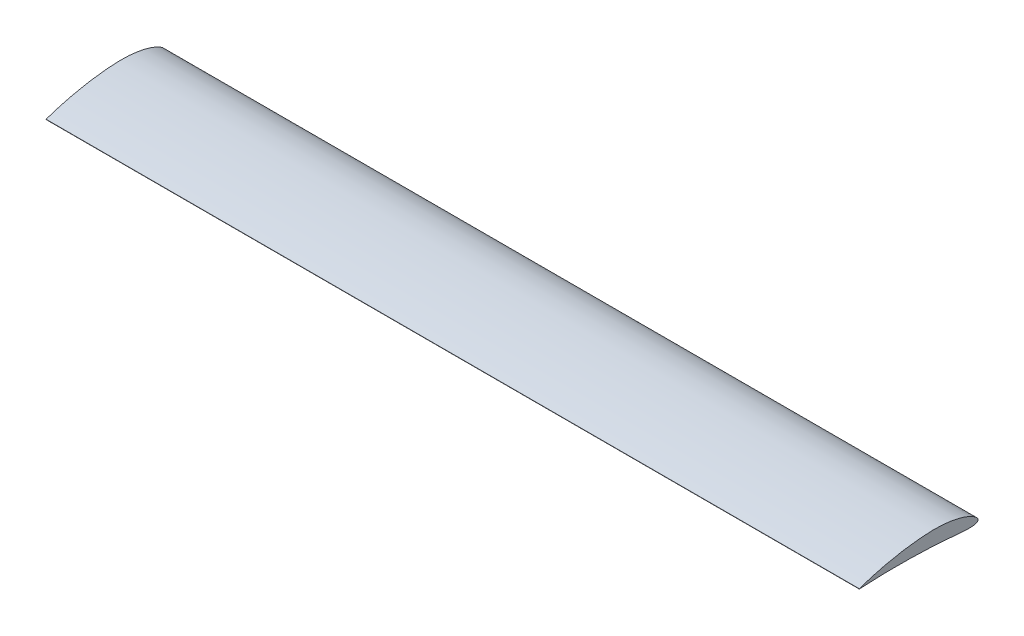
SolidWorks part; units mm, degrees
ref_plane "Front Plane" through (0, 0, 0) normal (0, 0, 1) x (1, 0, 0)
ref_plane "Top Plane" through (0, 0, 0) normal (0, 1, 0) x (1, 0, 0)
ref_plane "Right Plane" through (0, 0, 0) normal (1, 0, 0) x (0, 0, -1)
sketch3d "3DSketch3" plane through (0, 0, 0) normal (0, 0, 1) x (1, 0, 0)
  dimension "D1" = 2438.4
curve "Curve3"
  spline degree 3 poles (0, 0, 0) (0, -0.0634, 0.0198) (0, -0.1901, 0.0592) (0, -0.3772, 0.1273) (0, -0.5618, 0.2018) (0, -0.7437, 0.2832) (0, -0.923, 0.3715) (0, -1.0997, 0.4667) (0, -1.2737, 0.5687) (0, -1.4452, 0.6775) (0, -1.614, 0.7932) (0, -1.7802, 0.9157) (0, -1.9437, 1.045) (0, -2.1047, 1.181) (0, -2.2631, 1.3238) (0, -2.4188, 1.4735) (0, -2.5721, 1.6298) (0, -2.7222, 1.7933) (0, -2.8706, 1.9627) (0, -3.0158, 2.1392) (0, -3.1586, 2.3224) (0, -3.2988, 2.5123) (0, -3.4364, 2.7088) (0, -3.5714, 2.912) (0, -3.7039, 3.1219) (0, -3.8339, 3.3384) (0, -3.9613, 3.5614) (0, -4.0861, 3.7911) (0, -4.2084, 4.0274) (0, -4.3282, 4.2702) (0, -4.4454, 4.5196) (0, -4.5602, 4.7755) (0, -4.6724, 5.0379) (0, -4.7821, 5.3068) (0, -4.8894, 5.5822) (0, -4.9941, 5.8641) (0, -5.0964, 6.1524) (0, -5.1962, 6.4471) (0, -5.2935, 6.7483) (0, -5.3884, 7.0559) (0, -5.4809, 7.3698) (0, -5.5709, 7.6901) (0, -5.6585, 8.0167) (0, -5.7437, 8.3497) (0, -5.8264, 8.6889) (0, -5.9068, 9.0345) (0, -5.9848, 9.3863) (0, -6.0604, 9.7443) (0, -6.1337, 10.1086) (0, -6.2046, 10.4791) (0, -6.2732, 10.8558) (0, -6.3394, 11.2386) (0, -6.4033, 11.6276) (0, -6.4649, 12.0227) (0, -6.5242, 12.4239) (0, -6.5813, 12.8312) (0, -6.636, 13.2445) (0, -6.6885, 13.6639) (0, -6.7388, 14.0893) (0, -6.7868, 14.5207) (0, -6.8326, 14.958) (0, -6.8762, 15.4013) (0, -6.9176, 15.8506) (0, -6.9569, 16.3057) (0, -6.9939, 16.7667) (0, -7.0288, 17.2336) (0, -7.0616, 17.7063) (0, -7.0922, 18.1848) (0, -7.1208, 18.6691) (0, -7.1472, 19.1592) (0, -7.1716, 19.655) (0, -7.1939, 20.1565) (0, -7.2141, 20.6637) (0, -7.2323, 21.1766) (0, -7.2486, 21.6952) (0, -7.2628, 22.2193) (0, -7.275, 22.749) (0, -7.2852, 23.2844) (0, -7.2935, 23.8252) (0, -7.2999, 24.3716) (0, -7.3043, 24.9235) (0, -7.3069, 25.4808) (0, -7.3075, 26.0436) (0, -7.3063, 26.6118) (0, -7.3033, 27.1854) (0, -7.2984, 27.7644) (0, -7.2917, 28.3487) (0, -7.2832, 28.9383) (0, -7.273, 29.5332) (0, -7.2609, 30.1334) (0, -7.2472, 30.7389) (0, -7.2317, 31.3495) (0, -7.2145, 31.9653) (0, -7.1956, 32.5863) (0, -7.1751, 33.2124) (0, -7.1529, 33.8436) (0, -7.1291, 34.4799) (0, -7.1038, 35.1213) (0, -7.0768, 35.7677) (0, -7.0482, 36.4191) (0, -7.0182, 37.0755) (0, -6.9866, 37.7368) (0, -6.9534, 38.403) (0, -6.9189, 39.0741) (0, -6.8828, 39.7501) (0, -6.8453, 40.431) (0, -6.8064, 41.1166) (0, -6.7662, 41.807) (0, -6.7245, 42.5022) (0, -6.6815, 43.2022) (0, -6.6371, 43.9068) (0, -6.5915, 44.6161) (0, -6.5445, 45.3301) (0, -6.4963, 46.0486) (0, -6.4469, 46.7718) (0, -6.3962, 47.4996) (0, -6.3444, 48.2318) (0, -6.2914, 48.9686) (0, -6.2372, 49.7099) (0, -6.1819, 50.4557) (0, -6.1255, 51.2059) (0, -6.068, 51.9604) (0, -6.0095, 52.7194) (0, -5.9499, 53.4827) (0, -5.8894, 54.2503) (0, -5.8278, 55.0222) (0, -5.7653, 55.7984) (0, -5.7018, 56.5788) (0, -5.6375, 57.3635) (0, -5.5722, 58.1523) (0, -5.5061, 58.9453) (0, -5.4392, 59.7424) (0, -5.3714, 60.5436) (0, -5.3029, 61.3488) (0, -5.2336, 62.1581) (0, -5.1635, 62.9715) (0, -5.0927, 63.7888) (0, -5.0213, 64.6101) (0, -4.9492, 65.4353) (0, -4.8764, 66.2644) (0, -4.8031, 67.0974) (0, -4.7291, 67.9343) (0, -4.6546, 68.7749) (0, -4.5796, 69.6194) (0, -4.504, 70.4677) (0, -4.428, 71.3196) (0, -4.3515, 72.1753) (0, -4.2746, 73.0347) (0, -4.1972, 73.8977) (0, -4.1195, 74.7644) (0, -4.0414, 75.6346) (0, -3.9631, 76.5085) (0, -3.8844, 77.3858) (0, -3.8054, 78.2667) (0, -3.7262, 79.1511) (0, -3.6467, 80.0389) (0, -3.5671, 80.9302) (0, -3.4873, 81.8249) (0, -3.4073, 82.7229) (0, -3.3272, 83.6243) (0, -3.247, 84.529) (0, -3.1668, 85.437) (0, -3.0865, 86.3483) (0, -3.0062, 87.2628) (0, -2.926, 88.1805) (0, -2.8457, 89.1014) (0, -2.7656, 90.0255) (0, -2.6855, 90.9526) (0, -2.6055, 91.8829) (0, -2.5257, 92.8162) (0, -2.4461, 93.7526) (0, -2.3666, 94.692) (0, -2.2874, 95.6343) (0, -2.2084, 96.5796) (0, -2.1297, 97.5279) (0, -2.0514, 98.479) (0, -1.9733, 99.433) (0, -1.8956, 100.3898) (0, -1.8182, 101.3494) (0, -1.7413, 102.3118) (0, -1.6648, 103.277) (0, -1.5888, 104.2449) (0, -1.5132, 105.2155) (0, -1.4382, 106.1887) (0, -1.3636, 107.1646) (0, -1.2897, 108.1431) (0, -1.2163, 109.1241) (0, -1.1435, 110.1077) (0, -1.0714, 111.0938) (0, -0.9999, 112.0824) (0, -0.9291, 113.0735) (0, -0.8591, 114.067) (0, -0.7897, 115.0629) (0, -0.7211, 116.0611) (0, -0.6533, 117.0617) (0, -0.5863, 118.0646) (0, -0.5201, 119.0698) (0, -0.4548, 120.0772) (0, -0.3904, 121.0869) (0, -0.3268, 122.0987) (0, -0.2642, 123.1127) (0, -0.2025, 124.1288) (0, -0.1418, 125.147) (0, -0.0821, 126.1672) (0, -0.0234, 127.1895) (0, 0.0343, 128.2138) (0, 0.0908, 129.2401) (0, 0.1464, 130.2683) (0, 0.2008, 131.2984) (0, 0.2541, 132.3304) (0, 0.3062, 133.3643) (0, 0.3572, 134.3999) (0, 0.4069, 135.4374) (0, 0.4555, 136.4765) (0, 0.5028, 137.5174) (0, 0.5489, 138.56) (0, 0.5937, 139.6043) (0, 0.6372, 140.6501) (0, 0.6797, 141.7018) (0, 0.7205, 142.7639) (0, 0.7611, 143.8363) (0, 0.8019, 144.9147) (0, 0.8426, 145.9944) (0, 0.8833, 147.0755) (0, 0.9239, 148.1578) (0, 0.9644, 149.2414) (0, 1.0047, 150.3263) (0, 1.045, 151.4122) (0, 1.0852, 152.4994) (0, 1.1252, 153.5876) (0, 1.165, 154.6768) (0, 1.2047, 155.7671) (0, 1.2442, 156.8584) (0, 1.2835, 157.9505) (0, 1.3226, 159.0436) (0, 1.3615, 160.1375) (0, 1.4001, 161.2323) (0, 1.4385, 162.3278) (0, 1.4767, 163.424) (0, 1.5146, 164.5209) (0, 1.5522, 165.6185) (0, 1.5896, 166.7167) (0, 1.6266, 167.8154) (0, 1.6634, 168.9147) (0, 1.6998, 170.0145) (0, 1.7359, 171.1147) (0, 1.7717, 172.2153) (0, 1.8071, 173.3162) (0, 1.8422, 174.4175) (0, 1.8769, 175.5191) (0, 1.9113, 176.6209) (0, 1.9452, 177.7229) (0, 1.9788, 178.825) (0, 2.0119, 179.9273) (0, 2.0447, 181.0297) (0, 2.077, 182.132) (0, 2.1089, 183.2344) (0, 2.1404, 184.3367) (0, 2.1714, 185.4389) (0, 2.202, 186.541) (0, 2.2321, 187.6429) (0, 2.2617, 188.7446) (0, 2.2909, 189.846) (0, 2.3196, 190.9471) (0, 2.3478, 192.0478) (0, 2.3755, 193.1482) (0, 2.4027, 194.2482) (0, 2.4294, 195.3476) (0, 2.4556, 196.4466) (0, 2.4812, 197.545) (0, 2.5064, 198.6428) (0, 2.531, 199.7399) (0, 2.5551, 200.8364) (0, 2.5786, 201.9321) (0, 2.6016, 203.0271) (0, 2.624, 204.1213) (0, 2.6459, 205.2146) (0, 2.6672, 206.307) (0, 2.688, 207.3985) (0, 2.7082, 208.489) (0, 2.7278, 209.5785) (0, 2.7468, 210.6669) (0, 2.7653, 211.7542) (0, 2.7832, 212.8403) (0, 2.8005, 213.9253) (0, 2.8172, 215.009) (0, 2.8333, 216.0915) (0, 2.8488, 217.1726) (0, 2.8638, 218.2524) (0, 2.8781, 219.3307) (0, 2.8918, 220.4076) (0, 2.905, 221.483) (0, 2.9175, 222.5569) (0, 2.9294, 223.6292) (0, 2.9408, 224.6999) (0, 2.9515, 225.769) (0, 2.9616, 226.8363) (0, 2.9711, 227.9019) (0, 2.98, 228.9657) (0, 2.9883, 230.0277) (0, 2.996, 231.0878) (0, 3.0031, 232.146) (0, 3.0096, 233.2022) (0, 3.0155, 234.2564) (0, 3.0208, 235.3086) (0, 3.0255, 236.3587) (0, 3.0295, 237.4067) (0, 3.033, 238.4525) (0, 3.0359, 239.4962) (0, 3.0382, 240.5375) (0, 3.0399, 241.5766) (0, 3.0409, 242.6133) (0, 3.0414, 243.6477) (0, 3.0414, 244.6796) (0, 3.0407, 245.7091) (0, 3.0394, 246.7361) (0, 3.0376, 247.7605) (0, 3.0352, 248.7824) (0, 3.0322, 249.8016) (0, 3.0287, 250.8182) (0, 3.0245, 251.832) (0, 3.0199, 252.8431) (0, 3.0146, 253.8514) (0, 3.0088, 254.8569) (0, 3.0025, 255.8595) (0, 2.9956, 256.8592) (0, 2.9881, 257.856) (0, 2.9802, 258.8497) (0, 2.9716, 259.8404) (0, 2.9626, 260.828) (0, 2.953, 261.8126) (0, 2.943, 262.7939) (0, 2.9324, 263.7721) (0, 2.9213, 264.747) (0, 2.9097, 265.7186) (0, 2.8976, 266.6869) (0, 2.885, 267.6519) (0, 2.8719, 268.6135) (0, 2.8583, 269.5716) (0, 2.8443, 270.5262) (0, 2.8298, 271.4773) (0, 2.8148, 272.4249) (0, 2.7994, 273.3689) (0, 2.7835, 274.3092) (0, 2.7672, 275.2459) (0, 2.7505, 276.1788) (0, 2.7333, 277.108) (0, 2.7157, 278.0334) (0, 2.6977, 278.955) (0, 2.6793, 279.8726) (0, 2.6604, 280.7864) (0, 2.6412, 281.6963) (0, 2.6216, 282.6021) (0, 2.6016, 283.504) (0, 2.5813, 284.4017) (0, 2.5606, 285.2954) (0, 2.5395, 286.1849) (0, 2.518, 287.0703) (0, 2.4963, 287.9514) (0, 2.4742, 288.8283) (0, 2.4517, 289.701) (0, 2.429, 290.5693) (0, 2.4059, 291.4332) (0, 2.3825, 292.2927) (0, 2.3588, 293.1478) (0, 2.3349, 293.9985) (0, 2.3106, 294.8446) (0, 2.2861, 295.6862) (0, 2.2613, 296.5232) (0, 2.2363, 297.3556) (0, 2.211, 298.1834) (0, 2.1855, 299.0064) (0, 2.1597, 299.8248) (0, 2.1337, 300.6384) (0, 2.1075, 301.4472) (0, 2.0811, 302.2512) (0, 2.0545, 303.0503) (0, 2.0277, 303.8445) (0, 2.0008, 304.6338) (0, 1.9736, 305.4182) (0, 1.9463, 306.1975) (0, 1.9188, 306.9718) (0, 1.8912, 307.7411) (0, 1.8634, 308.5052) (0, 1.8355, 309.2643) (0, 1.8074, 310.0181) (0, 1.7793, 310.7668) (0, 1.751, 311.5103) (0, 1.7227, 312.2485) (0, 1.6942, 312.9814) (0, 1.6657, 313.709) (0, 1.6371, 314.4312) (0, 1.6084, 315.148) (0, 1.5796, 315.8594) (0, 1.5508, 316.5654) (0, 1.522, 317.2659) (0, 1.4931, 317.9609) (0, 1.4642, 318.6503) (0, 1.4353, 319.3342) (0, 1.4064, 320.0125) (0, 1.3774, 320.6851) (0, 1.3485, 321.3521) (0, 1.3195, 322.0133) (0, 1.2906, 322.6689) (0, 1.2618, 323.3187) (0, 1.2329, 323.9628) (0, 1.2041, 324.601) (0, 1.1754, 325.2334) (0, 1.1467, 325.86) (0, 1.118, 326.4806) (0, 1.0895, 327.0953) (0, 1.061, 327.7041) (0, 1.0326, 328.3069) (0, 1.0043, 328.9038) (0, 0.9761, 329.4946) (0, 0.9481, 330.0793) (0, 0.9201, 330.658) (0, 0.8923, 331.2305) (0, 0.8646, 331.797) (0, 0.837, 332.3572) (0, 0.8096, 332.9113) (0, 0.7823, 333.4592) (0, 0.7552, 334.0009) (0, 0.7282, 334.5363) (0, 0.7014, 335.0654) (0, 0.6748, 335.5883) (0, 0.6484, 336.1048) (0, 0.6222, 336.6149) (0, 0.5962, 337.1187) (0, 0.5704, 337.6161) (0, 0.5448, 338.1071) (0, 0.5194, 338.5916) (0, 0.4942, 339.0697) (0, 0.4693, 339.5413) (0, 0.4445, 340.0064) (0, 0.4201, 340.465) (0, 0.3959, 340.917) (0, 0.3719, 341.3625) (0, 0.3482, 341.8013) (0, 0.3247, 342.2336) (0, 0.3016, 342.6593) (0, 0.2787, 343.0782) (0, 0.2561, 343.4906) (0, 0.2337, 343.8962) (0, 0.2117, 344.2952) (0, 0.1899, 344.6874) (0, 0.1685, 345.0729) (0, 0.1473, 345.4516) (0, 0.1265, 345.8236) (0, 0.106, 346.1887) (0, 0.0858, 346.5471) (0, 0.0659, 346.8986) (0, 0.0464, 347.2433) (0, 0.027, 347.5812) (0, 0.0083, 347.9122) (0, -0.0102, 348.2362) (0, -0.0286, 348.5534) (0, -0.0462, 348.8637) (0, -0.0638, 349.167) (0, -0.0809, 349.4634) (0, -0.0977, 349.7529) (0, -0.1141, 350.0353) (0, -0.1301, 350.3108) (0, -0.1458, 350.5793) (0, -0.161, 350.8408) (0, -0.1759, 351.0952) (0, -0.1905, 351.3427) (0, -0.2046, 351.583) (0, -0.2183, 351.8164) (0, -0.2317, 352.0426) (0, -0.2447, 352.2618) (0, -0.2572, 352.4739) (0, -0.2694, 352.6789) (0, -0.2811, 352.8768) (0, -0.2925, 353.0675) (0, -0.3034, 353.2512) (0, -0.314, 353.4277) (0, -0.3241, 353.5971) (0, -0.3338, 353.7593) (0, -0.3431, 353.9144) (0, -0.352, 354.0623) (0, -0.3604, 354.203) (0, -0.3684, 354.3365) (0, -0.3761, 354.4629) (0, -0.3832, 354.5821) (0, -0.39, 354.6941) (0, -0.3963, 354.7989) (0, -0.4022, 354.8964) (0, -0.4077, 354.9868) (0, -0.4127, 355.07) (0, -0.4173, 355.1459) (0, -0.4214, 355.2146) (0, -0.4252, 355.2761) (0, -0.4285, 355.3304) (0, -0.4313, 355.3774) (0, -0.4337, 355.4172) (0, -0.4357, 355.4498) (0, -0.4372, 355.4751) (0, -0.4383, 355.4932) (0, -0.439, 355.5041) (0, -0.4393, 355.5089) (0, -0.4394, 355.5101) knots 0 0 0 0 0.000556 0.001111 0.001666 0.002222 0.00278 0.00334 0.003902 0.004469 0.00504 0.005616 0.006197 0.006785 0.00738 0.007983 0.008593 0.009214 0.009841 0.010479 0.011127 0.011786 0.012455 0.013136 0.013829 0.014533 0.01525 0.01598 0.016722 0.017478 0.018247 0.019029 0.019826 0.020637 0.021461 0.022301 0.023154 0.024023 0.024906 0.025805 0.026718 0.027647 0.028591 0.02955 0.030525 0.031515 0.032521 0.033542 0.034579 0.035632 0.036701 0.037785 0.038885 0.040001 0.041133 0.042281 0.043445 0.044625 0.04582 0.047032 0.048259 0.049503 0.050762 0.052037 0.053328 0.054635 0.055957 0.057296 0.05865 0.06002 0.061406 0.062807 0.064224 0.065656 0.067104 0.068568 0.070047 0.071541 0.073051 0.074576 0.076117 0.077673 0.079244 0.08083 0.082431 0.084047 0.085678 0.087324 0.088985 0.09066 0.092351 0.094056 0.095775 0.097509 0.099258 0.101021 0.102798 0.10459 0.106396 0.108216 0.11005 0.111898 0.11376 0.115636 0.117525 0.119428 0.121345 0.123276 0.12522 0.127177 0.129148 0.131132 0.133129 0.135139 0.137163 0.139199 0.141248 0.14331 0.145385 0.147472 0.149572 0.151684 0.153809 0.155946 0.158095 0.160257 0.16243 0.164616 0.166813 0.169023 0.171244 0.173476 0.175721 0.177977 0.180244 0.182523 0.184813 0.187114 0.189426 0.191749 0.194083 0.196428 0.198784 0.20115 0.203527 0.205915 0.208313 0.210721 0.21314 0.215569 0.218008 0.220456 0.222915 0.225384 0.227862 0.23035 0.232848 0.235355 0.237872 0.240398 0.242933 0.245478 0.248031 0.250593 0.253165 0.255745 0.258334 0.260932 0.263538 0.266153 0.268776 0.271407 0.274047 0.276695 0.27935 0.282014 0.284686 0.287366 0.290053 0.292748 0.29545 0.29816 0.300878 0.303602 0.306334 0.309073 0.311819 0.314572 0.317332 0.320099 0.322872 0.325652 0.328439 0.331232 0.334031 0.336836 0.339648 0.342466 0.34529 0.34812 0.350956 0.353797 0.356644 0.359497 0.362355 0.365219 0.368088 0.370962 0.373841 0.376726 0.379615 0.382509 0.385408 0.388312 0.391221 0.394134 0.397051 0.399973 0.402899 0.405865 0.408873 0.411885 0.414901 0.417921 0.420944 0.423971 0.427001 0.430035 0.433071 0.436111 0.439153 0.442199 0.445246 0.448297 0.45135 0.454405 0.457463 0.460523 0.463585 0.466648 0.469714 0.472781 0.475849 0.47892 0.481991 0.485064 0.488137 0.491212 0.494288 0.497364 0.500441 0.503518 0.506596 0.509674 0.512753 0.515831 0.518909 0.521987 0.525065 0.528142 0.531219 0.534296 0.537371 0.540445 0.543519 0.546591 0.549663 0.552733 0.555801 0.558868 0.561933 0.564996 0.568057 0.571117 0.574174 0.577228 0.580281 0.583331 0.586378 0.589422 0.592464 0.595502 0.598538 0.60157 0.604599 0.607624 0.610646 0.613664 0.616678 0.619688 0.622694 0.625696 0.628694 0.631687 0.634676 0.63766 0.64064 0.643614 0.646584 0.649548 0.652507 0.655461 0.658409 0.661352 0.664289 0.66722 0.670145 0.673065 0.675978 0.678884 0.681785 0.684679 0.687566 0.690446 0.69332 0.696186 0.699046 0.701898 0.704743 0.707581 0.710411 0.713233 0.716048 0.718854 0.721653 0.724443 0.727226 0.729999 0.732765 0.735522 0.73827 0.741009 0.74374 0.746461 0.749174 0.751877 0.75457 0.757255 0.759929 0.762594 0.765249 0.767895 0.77053 0.773155 0.77577 0.778374 0.780968 0.783552 0.786125 0.788687 0.791238 0.793778 0.796307 0.798825 0.801332 0.803827 0.806311 0.808783 0.811243 0.813691 0.816128 0.818552 0.820965 0.823365 0.825753 0.828128 0.830491 0.832841 0.835178 0.837503 0.839814 0.842113 0.844398 0.84667 0.848929 0.851174 0.853406 0.855624 0.857829 0.86002 0.862196 0.864359 0.866508 0.868642 0.870762 0.872868 0.874959 0.877036 0.879098 0.881145 0.883178 0.885195 0.887198 0.889185 0.891157 0.893114 0.895056 0.896982 0.898892 0.900787 0.902667 0.90453 0.906378 0.908209 0.910025 0.911824 0.913608 0.915375 0.917125 0.91886 0.920577 0.922279 0.923963 0.925631 0.927282 0.928916 0.930533 0.932133 0.933716 0.935282 0.93683 0.938362 0.939875 0.941372 0.942851 0.944312 0.945756 0.947181 0.94859 0.94998 0.951352 0.952707 0.954043 0.955361 0.956661 0.957943 0.959206 0.960452 0.961678 0.962887 0.964077 0.965248 0.966401 0.967535 0.96865 0.969746 0.970824 0.971883 0.972923 0.973944 0.974945 0.975928 0.976892 0.977837 0.978762 0.979668 0.980555 0.981422 0.98227 0.983099 0.983908 0.984698 0.985468 0.986219 0.98695 0.987662 0.988353 0.989026 0.989678 0.990311 0.990923 0.991517 0.99209 0.992643 0.993177 0.99369 0.994184 0.994657 0.995111 0.995544 0.995958 0.996352 0.996725 0.997078 0.997412 0.997725 0.998018 0.998291 0.998543 0.998776 0.998988 0.99918 0.999352 0.999504 0.999636 0.999747 0.999838 0.999909 0.99996 0.99999 1 1 1 1
curve "Curve4"
  spline degree 3 poles (0, 0, 0) (0, 0.0638, -0.0184) (0, 0.1913, -0.0552) (0, 0.385, -0.1013) (0, 0.5801, -0.1407) (0, 0.7768, -0.1727) (0, 0.9752, -0.1976) (0, 1.1751, -0.2151) (0, 1.3767, -0.2255) (0, 1.5798, -0.2285) (0, 1.7845, -0.2243) (0, 1.9908, -0.2128) (0, 2.1987, -0.1941) (0, 2.4081, -0.168) (0, 2.6191, -0.1347) (0, 2.8317, -0.0941) (0, 3.0458, -0.0461) (0, 3.2614, 0.0091) (0, 3.4786, 0.0716) (0, 3.6973, 0.1414) (0, 3.9175, 0.2185) (0, 4.1392, 0.303) (0, 4.3625, 0.3947) (0, 4.5872, 0.4938) (0, 4.8133, 0.6002) (0, 5.041, 0.7139) (0, 5.2701, 0.8349) (0, 5.5006, 0.9632) (0, 5.7325, 1.0989) (0, 5.9659, 1.2419) (0, 6.2006, 1.3922) (0, 6.4368, 1.5498) (0, 6.6743, 1.7147) (0, 6.9131, 1.887) (0, 7.1533, 2.0666) (0, 7.3948, 2.2535) (0, 7.6375, 2.4477) (0, 7.8816, 2.6493) (0, 8.1269, 2.8582) (0, 8.3735, 3.0743) (0, 8.6213, 3.2978) (0, 8.8703, 3.5286) (0, 9.1204, 3.7667) (0, 9.3718, 4.0122) (0, 9.6242, 4.2649) (0, 9.8778, 4.5249) (0, 10.1325, 4.7921) (0, 10.3882, 5.0667) (0, 10.645, 5.3486) (0, 10.9028, 5.6377) (0, 11.1616, 5.9341) (0, 11.4214, 6.2378) (0, 11.6822, 6.5487) (0, 11.9438, 6.8668) (0, 12.2064, 7.1922) (0, 12.4698, 7.5249) (0, 12.734, 7.8648) (0, 12.9991, 8.2118) (0, 13.265, 8.5661) (0, 13.5316, 8.9276) (0, 13.7989, 9.2963) (0, 14.067, 9.6722) (0, 14.3357, 10.0553) (0, 14.6051, 10.4455) (0, 14.875, 10.8428) (0, 15.1456, 11.2473) (0, 15.4167, 11.659) (0, 15.6883, 12.0777) (0, 15.9604, 12.5036) (0, 16.233, 12.9366) (0, 16.5059, 13.3766) (0, 16.7793, 13.8237) (0, 17.0531, 14.2779) (0, 17.3271, 14.7391) (0, 17.6015, 15.2073) (0, 17.8761, 15.6825) (0, 18.1509, 16.1648) (0, 18.4259, 16.654) (0, 18.7011, 17.1502) (0, 18.9764, 17.6533) (0, 19.2518, 18.1634) (0, 19.5272, 18.6804) (0, 19.8026, 19.2042) (0, 20.078, 19.735) (0, 20.3534, 20.2726) (0, 20.6287, 20.8171) (0, 20.9038, 21.3684) (0, 21.1787, 21.9265) (0, 21.4535, 22.4914) (0, 21.728, 23.0631) (0, 22.0023, 23.6415) (0, 22.2762, 24.2266) (0, 22.5498, 24.8185) (0, 22.8229, 25.417) (0, 23.0957, 26.0222) (0, 23.368, 26.634) (0, 23.6398, 27.2524) (0, 23.911, 27.8775) (0, 24.1817, 28.5091) (0, 24.4517, 29.1472) (0, 24.7211, 29.7919) (0, 24.9898, 30.443) (0, 25.2577, 31.1007) (0, 25.5249, 31.7648) (0, 25.7913, 32.4353) (0, 26.0568, 33.1122) (0, 26.3214, 33.7954) (0, 26.5851, 34.485) (0, 26.8478, 35.1809) (0, 27.1096, 35.8831) (0, 27.3702, 36.5916) (0, 27.6298, 37.3062) (0, 27.8883, 38.0271) (0, 28.1456, 38.7542) (0, 28.4017, 39.4873) (0, 28.6566, 40.2266) (0, 28.9102, 40.972) (0, 29.1625, 41.7234) (0, 29.4134, 42.4808) (0, 29.6629, 43.2442) (0, 29.911, 44.0136) (0, 30.1577, 44.7888) (0, 30.4028, 45.57) (0, 30.6464, 46.357) (0, 30.8884, 47.1498) (0, 31.1287, 47.9484) (0, 31.3674, 48.7528) (0, 31.6044, 49.5628) (0, 31.8397, 50.3786) (0, 32.0732, 51.2) (0, 32.3049, 52.0269) (0, 32.5347, 52.8595) (0, 32.7627, 53.6976) (0, 32.9887, 54.5412) (0, 33.2128, 55.3902) (0, 33.4349, 56.2446) (0, 33.6549, 57.1045) (0, 33.8729, 57.9697) (0, 34.0888, 58.8401) (0, 34.3026, 59.7159) (0, 34.5141, 60.5968) (0, 34.7235, 61.483) (0, 34.9306, 62.3743) (0, 35.1355, 63.2707) (0, 35.338, 64.1721) (0, 35.5382, 65.0786) (0, 35.736, 65.99) (0, 35.9314, 66.9064) (0, 36.1244, 67.8277) (0, 36.3149, 68.7538) (0, 36.5029, 69.6847) (0, 36.6883, 70.6204) (0, 36.8712, 71.5608) (0, 37.0514, 72.5059) (0, 37.229, 73.4556) (0, 37.404, 74.4099) (0, 37.5762, 75.3688) (0, 37.7458, 76.3321) (0, 37.9125, 77.2999) (0, 38.0765, 78.2721) (0, 38.2377, 79.2486) (0, 38.396, 80.2295) (0, 38.5514, 81.2146) (0, 38.704, 82.204) (0, 38.8536, 83.1975) (0, 39.0002, 84.1951) (0, 39.1439, 85.1968) (0, 39.2846, 86.2026) (0, 39.4222, 87.2123) (0, 39.5567, 88.2259) (0, 39.6882, 89.2434) (0, 39.8166, 90.2648) (0, 39.9418, 91.2899) (0, 40.0639, 92.3188) (0, 40.1828, 93.3514) (0, 40.2985, 94.3876) (0, 40.4109, 95.4274) (0, 40.5202, 96.4707) (0, 40.6261, 97.5175) (0, 40.7287, 98.5677) (0, 40.8281, 99.6213) (0, 40.9241, 100.6783) (0, 41.0167, 101.7385) (0, 41.106, 102.8019) (0, 41.1919, 103.8686) (0, 41.2744, 104.9383) (0, 41.3534, 106.0112) (0, 41.429, 107.087) (0, 41.5011, 108.1658) (0, 41.5698, 109.2476) (0, 41.635, 110.3322) (0, 41.6966, 111.4196) (0, 41.7548, 112.5098) (0, 41.8094, 113.6026) (0, 41.8604, 114.6982) (0, 41.9079, 115.7963) (0, 41.9518, 116.897) (0, 41.9921, 118.0002) (0, 42.0288, 119.1058) (0, 42.0619, 120.2138) (0, 42.0913, 121.3241) (0, 42.1173, 122.4368) (0, 42.139, 123.5516) (0, 42.1592, 124.6686) (0, 42.1676, 125.7878) (0, 42.1543, 126.9092) (0, 42.1994, 128.032) (0, 42.1931, 129.1574) (0, 42.196, 130.2845) (0, 42.1917, 131.4134) (0, 42.1846, 132.5441) (0, 42.1736, 133.6766) (0, 42.1589, 134.8108) (0, 42.1405, 135.9466) (0, 42.1183, 137.0839) (0, 42.0925, 138.2228) (0, 42.0629, 139.3632) (0, 42.0295, 140.505) (0, 41.9927, 141.6439) (0, 41.9519, 142.7753) (0, 41.9085, 143.8991) (0, 41.8633, 145.0197) (0, 41.8158, 146.1414) (0, 41.7661, 147.2644) (0, 41.7142, 148.3885) (0, 41.66, 149.5137) (0, 41.6037, 150.64) (0, 41.5452, 151.7672) (0, 41.4845, 152.8954) (0, 41.4216, 154.0245) (0, 41.3565, 155.1544) (0, 41.2893, 156.2851) (0, 41.2199, 157.4166) (0, 41.1484, 158.5488) (0, 41.0747, 159.6817) (0, 40.9989, 160.8151) (0, 40.921, 161.9492) (0, 40.841, 163.0837) (0, 40.7588, 164.2187) (0, 40.6746, 165.3541) (0, 40.5883, 166.4899) (0, 40.4999, 167.626) (0, 40.4094, 168.7624) (0, 40.3169, 169.8991) (0, 40.2223, 171.0359) (0, 40.1257, 172.1728) (0, 40.0271, 173.3098) (0, 39.9265, 174.4469) (0, 39.8238, 175.5839) (0, 39.7192, 176.7209) (0, 39.6126, 177.8578) (0, 39.504, 178.9945) (0, 39.3935, 180.1311) (0, 39.281, 181.2674) (0, 39.1666, 182.4033) (0, 39.0503, 183.539) (0, 38.9321, 184.6743) (0, 38.8119, 185.8091) (0, 38.6899, 186.9434) (0, 38.5661, 188.0773) (0, 38.4404, 189.2105) (0, 38.3128, 190.3431) (0, 38.1834, 191.4751) (0, 38.0523, 192.6063) (0, 37.9193, 193.7368) (0, 37.7845, 194.8665) (0, 37.648, 195.9953) (0, 37.5097, 197.1232) (0, 37.3697, 198.2502) (0, 37.228, 199.3761) (0, 37.0845, 200.5011) (0, 36.9394, 201.6249) (0, 36.7926, 202.7477) (0, 36.6441, 203.8692) (0, 36.494, 204.9895) (0, 36.3423, 206.1086) (0, 36.1889, 207.2263) (0, 36.034, 208.3427) (0, 35.8775, 209.4577) (0, 35.7194, 210.5712) (0, 35.5598, 211.6833) (0, 35.3986, 212.7938) (0, 35.236, 213.9027) (0, 35.0718, 215.01) (0, 34.9062, 216.1157) (0, 34.7391, 217.2196) (0, 34.5706, 218.3217) (0, 34.4007, 219.4221) (0, 34.2293, 220.5206) (0, 34.0566, 221.6172) (0, 33.8825, 222.7119) (0, 33.707, 223.8046) (0, 33.5303, 224.8953) (0, 33.3522, 225.9839) (0, 33.1728, 227.0704) (0, 32.9921, 228.1547) (0, 32.8102, 229.2369) (0, 32.6271, 230.3168) (0, 32.4427, 231.3944) (0, 32.2571, 232.4697) (0, 32.0704, 233.5427) (0, 31.8825, 234.6132) (0, 31.6935, 235.6813) (0, 31.5033, 236.7469) (0, 31.3121, 237.81) (0, 31.1197, 238.8704) (0, 30.9263, 239.9283) (0, 30.7319, 240.9835) (0, 30.5365, 242.036) (0, 30.34, 243.0858) (0, 30.1426, 244.1328) (0, 29.9443, 245.1769) (0, 29.7449, 246.2182) (0, 29.5447, 247.2566) (0, 29.3436, 248.2921) (0, 29.1416, 249.3245) (0, 28.9388, 250.354) (0, 28.7351, 251.3804) (0, 28.5307, 252.4036) (0, 28.3254, 253.4238) (0, 28.1194, 254.4407) (0, 27.9126, 255.4544) (0, 27.7051, 256.4649) (0, 27.4969, 257.472) (0, 27.2881, 258.4759) (0, 27.0785, 259.4763) (0, 26.8684, 260.4733) (0, 26.6576, 261.4669) (0, 26.4463, 262.457) (0, 26.2343, 263.4435) (0, 26.0219, 264.4265) (0, 25.8089, 265.4059) (0, 25.5954, 266.3816) (0, 25.3814, 267.3537) (0, 25.167, 268.322) (0, 24.9521, 269.2866) (0, 24.7368, 270.2474) (0, 24.5212, 271.2043) (0, 24.3051, 272.1574) (0, 24.0888, 273.1066) (0, 23.8721, 274.0519) (0, 23.6551, 274.9932) (0, 23.4378, 275.9305) (0, 23.2203, 276.8637) (0, 23.0026, 277.7929) (0, 22.7847, 278.718) (0, 22.5665, 279.6389) (0, 22.3483, 280.5556) (0, 22.1299, 281.4682) (0, 21.9113, 282.3764) (0, 21.6927, 283.2804) (0, 21.4741, 284.1801) (0, 21.2553, 285.0754) (0, 21.0366, 285.9664) (0, 20.8179, 286.8529) (0, 20.5992, 287.735) (0, 20.3805, 288.6126) (0, 20.162, 289.4856) (0, 19.9435, 290.3542) (0, 19.7252, 291.2181) (0, 19.507, 292.0775) (0, 19.2889, 292.9322) (0, 19.0711, 293.7822) (0, 18.8535, 294.6275) (0, 18.6361, 295.4681) (0, 18.419, 296.3039) (0, 18.2022, 297.1349) (0, 17.9857, 297.9611) (0, 17.7695, 298.7825) (0, 17.5537, 299.5989) (0, 17.3383, 300.4104) (0, 17.1233, 301.217) (0, 16.9087, 302.0186) (0, 16.6945, 302.8152) (0, 16.4809, 303.6068) (0, 16.2677, 304.3933) (0, 16.0551, 305.1747) (0, 15.843, 305.951) (0, 15.6315, 306.7221) (0, 15.4205, 307.4881) (0, 15.2102, 308.2488) (0, 15.0006, 309.0043) (0, 14.7916, 309.7546) (0, 14.5833, 310.4996) (0, 14.3757, 311.2392) (0, 14.1688, 311.9736) (0, 13.9627, 312.7025) (0, 13.7573, 313.4261) (0, 13.5528, 314.1443) (0, 13.3491, 314.857) (0, 13.1463, 315.5642) (0, 12.9443, 316.266) (0, 12.7432, 316.9622) (0, 12.543, 317.6529) (0, 12.3438, 318.338) (0, 12.1455, 319.0176) (0, 11.9482, 319.6915) (0, 11.752, 320.3598) (0, 11.5567, 321.0224) (0, 11.3625, 321.6793) (0, 11.1694, 322.3306) (0, 10.9774, 322.9761) (0, 10.7865, 323.6158) (0, 10.5967, 324.2498) (0, 10.4081, 324.8779) (0, 10.2207, 325.5003) (0, 10.0345, 326.1168) (0, 9.8495, 326.7274) (0, 9.6658, 327.3322) (0, 9.4833, 327.931) (0, 9.3021, 328.5239) (0, 9.1223, 329.1109) (0, 8.9437, 329.6919) (0, 8.7665, 330.2669) (0, 8.5907, 330.8359) (0, 8.4163, 331.3989) (0, 8.2433, 331.9558) (0, 8.0718, 332.5067) (0, 7.9016, 333.0515) (0, 7.733, 333.5902) (0, 7.5659, 334.1227) (0, 7.4002, 334.6492) (0, 7.2362, 335.1694) (0, 7.0736, 335.6835) (0, 6.9126, 336.1914) (0, 6.7533, 336.6931) (0, 6.5955, 337.1885) (0, 6.4394, 337.6777) (0, 6.2849, 338.1607) (0, 6.1321, 338.6374) (0, 5.9809, 339.1078) (0, 5.8315, 339.5718) (0, 5.6838, 340.0296) (0, 5.5378, 340.481) (0, 5.3936, 340.926) (0, 5.2511, 341.3647) (0, 5.1105, 341.797) (0, 4.9716, 342.2229) (0, 4.8346, 342.6424) (0, 4.6994, 343.0554) (0, 4.5661, 343.462) (0, 4.4346, 343.8622) (0, 4.305, 344.2559) (0, 4.1774, 344.6431) (0, 4.0516, 345.0238) (0, 3.9278, 345.398) (0, 3.8059, 345.7657) (0, 3.686, 346.1268) (0, 3.5681, 346.4814) (0, 3.4521, 346.8294) (0, 3.3385, 347.171) (0, 3.2253, 347.5055) (0, 3.12, 347.8366) (0, 2.9939, 348.1528) (0, 2.8977, 348.4717) (0, 2.7952, 348.7798) (0, 2.6918, 349.0804) (0, 2.5994, 349.3774) (0, 2.5004, 349.6649) (0, 2.4056, 349.947) (0, 2.3123, 350.2222) (0, 2.2214, 350.4907) (0, 2.1326, 350.7526) (0, 2.0459, 351.0078) (0, 1.9614, 351.2562) (0, 1.8792, 351.498) (0, 1.7991, 351.733) (0, 1.7212, 351.9613) (0, 1.6456, 352.1828) (0, 1.5722, 352.3977) (0, 1.501, 352.6057) (0, 1.432, 352.807) (0, 1.3654, 353.0016) (0, 1.3009, 353.1894) (0, 1.2388, 353.3704) (0, 1.1789, 353.5446) (0, 1.1214, 353.712) (0, 1.0661, 353.8727) (0, 1.0131, 354.0265) (0, 0.9624, 354.1736) (0, 0.9141, 354.3138) (0, 0.8681, 354.4472) (0, 0.8243, 354.5738) (0, 0.783, 354.6936) (0, 0.7439, 354.8066) (0, 0.7072, 354.9127) (0, 0.6729, 355.012) (0, 0.6409, 355.1045) (0, 0.6112, 355.1901) (0, 0.5839, 355.2689) (0, 0.559, 355.3408) (0, 0.5364, 355.4059) (0, 0.5162, 355.4642) (0, 0.4984, 355.5156) (0, 0.483, 355.5602) (0, 0.4699, 355.5979) (0, 0.4592, 355.6287) (0, 0.4509, 355.6527) (0, 0.4449, 355.6698) (0, 0.4413, 355.6801) (0, 0.4397, 355.6847) (0, 0.4394, 355.6858) knots 0 0 0 0 0.000533 0.001065 0.001598 0.002131 0.002665 0.003202 0.003742 0.004285 0.004833 0.005386 0.005944 0.006508 0.00708 0.007659 0.008245 0.008841 0.009445 0.01006 0.010684 0.011319 0.011964 0.012621 0.01329 0.013971 0.014664 0.01537 0.016089 0.016821 0.017567 0.018327 0.0191 0.019888 0.020691 0.021508 0.02234 0.023187 0.024049 0.024927 0.02582 0.026728 0.027653 0.028593 0.029548 0.03052 0.031508 0.032513 0.033533 0.03457 0.035623 0.036692 0.037778 0.03888 0.039999 0.041135 0.042287 0.043456 0.044641 0.045843 0.047062 0.048297 0.04955 0.050819 0.052104 0.053407 0.054726 0.056061 0.057414 0.058783 0.060169 0.061571 0.062991 0.064426 0.065879 0.067348 0.068833 0.070335 0.071853 0.073388 0.07494 0.076507 0.078091 0.079692 0.081308 0.082941 0.08459 0.086255 0.087936 0.089633 0.091346 0.093075 0.09482 0.096581 0.098358 0.10015 0.101958 0.103781 0.10562 0.107475 0.109344 0.11123 0.11313 0.115046 0.116977 0.118923 0.120884 0.122859 0.12485 0.126856 0.128876 0.130911 0.13296 0.135024 0.137103 0.139196 0.141303 0.143424 0.145559 0.147709 0.149872 0.152049 0.15424 0.156445 0.158664 0.160896 0.163141 0.1654 0.167672 0.169957 0.172256 0.174567 0.176892 0.179229 0.181579 0.183942 0.186317 0.188705 0.191105 0.193517 0.195942 0.198379 0.200828 0.203289 0.205761 0.208246 0.210742 0.213249 0.215768 0.218299 0.220841 0.223393 0.225957 0.228532 0.231118 0.233714 0.236322 0.238939 0.241568 0.244206 0.246855 0.249514 0.252183 0.254862 0.257551 0.26025 0.262958 0.265676 0.268403 0.271139 0.273885 0.27664 0.279404 0.282177 0.284959 0.287749 0.290548 0.293355 0.296171 0.298995 0.301827 0.304668 0.307516 0.310372 0.313236 0.316107 0.318986 0.321873 0.324766 0.327667 0.330575 0.33349 0.336412 0.33934 0.342275 0.345217 0.348165 0.351119 0.35408 0.357046 0.360019 0.362997 0.365982 0.368971 0.371967 0.374967 0.377974 0.380985 0.384002 0.387023 0.390049 0.39308 0.396116 0.399156 0.4022 0.405249 0.408302 0.411359 0.41442 0.417451 0.420448 0.42345 0.426455 0.429463 0.432474 0.435489 0.438507 0.441528 0.444552 0.447578 0.450607 0.453639 0.456672 0.459708 0.462747 0.465787 0.468829 0.471873 0.474918 0.477965 0.481014 0.484064 0.487114 0.490166 0.493219 0.496273 0.499327 0.502382 0.505438 0.508493 0.511549 0.514605 0.517661 0.520717 0.523773 0.526828 0.529883 0.532937 0.53599 0.539043 0.542094 0.545144 0.548194 0.551241 0.554288 0.557332 0.560375 0.563417 0.566456 0.569493 0.572528 0.575561 0.578591 0.581619 0.584644 0.587666 0.590685 0.593702 0.596715 0.599725 0.602732 0.605735 0.608734 0.61173 0.614722 0.61771 0.620694 0.623674 0.626649 0.62962 0.632587 0.635548 0.638506 0.641458 0.644405 0.647347 0.650284 0.653215 0.656141 0.659061 0.661976 0.664885 0.667788 0.670684 0.673575 0.67646 0.679338 0.682209 0.685074 0.687932 0.690784 0.693628 0.696465 0.699296 0.702119 0.704934 0.707742 0.710543 0.713335 0.71612 0.718897 0.721666 0.724426 0.727179 0.729923 0.732658 0.735385 0.738104 0.740813 0.743513 0.746205 0.748887 0.75156 0.754224 0.756878 0.759523 0.762158 0.764783 0.767399 0.770004 0.7726 0.775185 0.77776 0.780324 0.782879 0.785422 0.787955 0.790477 0.792988 0.795488 0.797977 0.800455 0.802922 0.805377 0.807821 0.810253 0.812673 0.815082 0.817479 0.819863 0.822236 0.824597 0.826945 0.829281 0.831605 0.833916 0.836215 0.8385 0.840773 0.843033 0.84528 0.847514 0.849735 0.851943 0.854137 0.856318 0.858485 0.860639 0.862779 0.864905 0.867017 0.869116 0.8712 0.87327 0.875326 0.877368 0.879396 0.881409 0.883407 0.885391 0.88736 0.889314 0.891254 0.893178 0.895088 0.896982 0.898861 0.900725 0.902574 0.904407 0.906225 0.908028 0.909814 0.911585 0.913341 0.91508 0.916804 0.918511 0.920203 0.921878 0.923537 0.92518 0.926807 0.928417 0.930011 0.931588 0.933149 0.934693 0.936221 0.937731 0.939225 0.940702 0.942162 0.943605 0.945031 0.94644 0.947831 0.949206 0.950563 0.951902 0.953225 0.954529 0.955817 0.957086 0.958338 0.959573 0.960789 0.961988 0.963169 0.964332 0.965477 0.966605 0.967714 0.968805 0.969878 0.970933 0.97197 0.972988 0.973988 0.97497 0.975933 0.976878 0.977805 0.978722 0.979608 0.980478 0.98133 0.98216 0.982975 0.983771 0.984549 0.985308 0.986048 0.986769 0.987471 0.988155 0.988819 0.989465 0.990091 0.990699 0.991287 0.991857 0.992407 0.992939 0.993451 0.993944 0.994418 0.994872 0.995308 0.995724 0.996121 0.996499 0.996857 0.997196 0.997516 0.997817 0.998098 0.99836 0.998602 0.998825 0.999029 0.999214 0.999379 0.999524 0.99965 0.999757 0.999845 0.999913 0.999961 0.99999 1 1 1 1
sketch "Sketch1" plane through (0, 0, 0) normal (1, 0, 0) x (0, 0, -1)
  arc A0 (-355.6858, 0.4394) -> (-355.5101, -0.4394) centre (-355.598, 0) ccw
  spline S0 degree 3 poles (4752.6647, -1547.1568) (-26.3578, 29.3158) (3.2903, 9.0146) (-0.1273, -0.3772) (-0.2018, -0.5618) (-0.2832, -0.7437) (-0.4012, -0.9833) (-0.5329, -1.2173) (-0.6775, -1.4452) (-0.8325, -1.6713) (-1.0005, -1.8912) (-1.181, -2.1047) (-1.3238, -2.2631) (-1.4735, -2.4188) (-1.6298, -2.5721) (-1.7933, -2.7222) (-1.9627, -2.8706) (-2.1392, -3.0158) (-2.3224, -3.1586) (-2.5777, -3.3471) (-2.8444, -3.5288) (-3.1943, -3.7496) (-3.4875, -3.9211) (-3.8704, -4.1292) (-4.2734, -4.3326) (-4.779, -4.5644) (-5.3107, -4.7862) (-5.8682, -4.998) (-6.4515, -5.1999) (-7.0604, -5.392) (-7.6948, -5.5743) (-8.3546, -5.7469) (-9.0395, -5.9099) (-9.7495, -6.0633) (-10.4843, -6.2073) (-11.2439, -6.342) (-12.0281, -6.4674) (-12.8366, -6.5836) (-13.6694, -6.6907) (-14.5262, -6.7889) (-15.4069, -6.8781) (-16.3112, -6.9586) (-17.2391, -7.0305) (-18.1904, -7.0938) (-19.1647, -7.1487) (-20.1621, -7.1953) (-21.3587, -7.2403) (-22.7637, -7.2781) (-24.3862, -7.3027) (-26.0581, -7.31) (-27.7787, -7.3006) (-29.5474, -7.2749) (-31.3635, -7.2334) (-33.2262, -7.1766) (-35.1349, -7.105) (-37.0889, -7.0192) (-39.0874, -6.9198) (-41.1296, -6.8072) (-43.215, -6.6821) (-45.5868, -6.5292) (-48.2549, -6.3449) (-51.2283, -6.1257) (-54.2722, -5.8892) (-57.3847, -5.6371) (-60.5642, -5.3708) (-63.8088, -5.0919) (-67.1168, -4.802) (-70.4864, -4.5027) (-74.2095, -4.1695) (-78.2945, -3.8026) (-82.7495, -3.4042) (-87.2882, -3.0028) (-91.907, -2.6018) (-96.6025, -2.2045) (-101.3711, -1.814) (-106.2091, -1.4337) (-111.4464, -1.0417) (-117.426, -0.6222) (-122.1112, -0.3228) (-125.147, -0.1418) (-126.1672, -0.0821) (-127.1895, -0.0234) (-128.2138, 0.0343) (-129.2401, 0.0908) (-130.9568, 0.1835) (-133.7157, 0.326) (-136.4798, 0.457) (-138.56, 0.5489) (-139.6043, 0.5937) (-140.6501, 0.6372) (-141.7018, 0.6797) (-142.7639, 0.7205) (-143.8363, 0.7611) (-144.9147, 0.8019) (-146.7164, 0.8698) (-151.0617, 1.0328) (-157.2371, 1.2597) (-164.8952, 1.5295) (-172.2208, 1.7748) (-179.9282, 2.0153) (-187.639, 2.2357) (-195.3391, 2.4332) (-203.0139, 2.6056) (-210.6489, 2.751) (-218.5854, 2.8736) (-226.7995, 2.9675) (-235.2648, 3.0268) (-243.5969, 3.0476) (-252.1036, 3.0301) (-260.7451, 2.9708) (-269.4791, 2.8666) (-278.2268, 2.7192) (-287.211, 2.5227) (-296.5993, 2.2676) (-305.9588, 1.9627) (-315.3182, 1.6092) (-324.5863, 1.2126) (-333.7568, 0.7743) (-340.5803, 0.4167) (-344.5208, 0.1994) (-345.6973, 0.1336) (-346.1887, 0.106) (-346.5471, 0.0858) (-346.8986, 0.0659) (-347.2433, 0.0464) (-347.5812, 0.027) (-347.9122, 0.0083) (-348.2362, -0.0102) (-348.5534, -0.0286) (-348.8637, -0.0462) (-349.167, -0.0638) (-349.5576, -0.0863) (-350.3629, -0.1331) (-351.9429, -0.2255) (-353.6898, -0.3294) (-354.9871, -0.4076) (-355.4172, -0.4337) (-355.4932, -0.4383) (-374.664, -1.6018) (-393.8478, -2.4506) (-110.1537, -4993.2029) knots -0.081994 -0.081994 -0.081994 -0.081994 0.000556 0.001111 0.001666 0.002222 0.00278 0.003902 0.004469 0.00504 0.006197 0.006785 0.00738 0.007983 0.008593 0.009214 0.009841 0.010479 0.011127 0.011786 0.013136 0.013829 0.01525 0.01598 0.017478 0.019029 0.020637 0.022301 0.024023 0.025805 0.027647 0.02955 0.031515 0.033542 0.035632 0.037785 0.040001 0.042281 0.044625 0.047032 0.049503 0.052037 0.054635 0.057296 0.06002 0.062807 0.065656 0.070047 0.074576 0.079244 0.084047 0.088985 0.094056 0.099258 0.10459 0.11005 0.115636 0.121345 0.127177 0.133129 0.141248 0.149572 0.158095 0.166813 0.175721 0.184813 0.194083 0.203527 0.21314 0.225384 0.237872 0.250593 0.263538 0.276695 0.290053 0.303602 0.317332 0.334031 0.353797 0.356644 0.359497 0.362355 0.365219 0.368088 0.370962 0.379615 0.391221 0.394134 0.397051 0.399973 0.402899 0.405865 0.408873 0.411885 0.414901 0.423971 0.448297 0.466648 0.488137 0.509674 0.531219 0.552733 0.574174 0.595502 0.616678 0.64064 0.664289 0.687566 0.710411 0.735522 0.759929 0.783552 0.808783 0.835178 0.862196 0.887198 0.913608 0.939875 0.964077 0.970824 0.972923 0.973944 0.974945 0.975928 0.976892 0.977837 0.978762 0.979668 0.980555 0.981422 0.98227 0.983099 0.984698 0.989026 0.996352 0.999352 0.999909 0.99996 0.99999 1.160736 1.160736 1.160736 1.160736 only from (0, 0) to (-355.5101, -0.4394) construction
  spline S1 degree 3 poles (4819.2495, -1324.3094) (-38.1571, -9.9504) (-2.2131, -9.3316) (0.1013, 0.385) (0.1407, 0.5801) (0.1727, 0.7768) (0.2059, 1.0419) (0.2245, 1.3098) (0.2285, 1.5798) (0.2243, 1.7845) (0.2089, 2.061) (0.1789, 2.3394) (0.1347, 2.6191) (0.0941, 2.8317) (0.0461, 3.0458) (-0.0091, 3.2614) (-0.0716, 3.4786) (-0.1414, 3.6973) (-0.2451, 3.9934) (-0.3628, 4.2901) (-0.528, 4.6648) (-0.6749, 4.9673) (-0.8767, 5.3492) (-1.0529, 5.6575) (-1.2913, 6.0466) (-1.5506, 6.4426) (-1.8882, 6.919) (-2.255, 7.4006) (-2.6511, 7.8875) (-3.0764, 8.3794) (-3.531, 8.8761) (-4.0148, 9.3775) (-4.5277, 9.8835) (-5.0698, 10.3939) (-5.6409, 10.9084) (-6.2412, 11.4269) (-6.8704, 11.9492) (-7.5286, 12.4751) (-8.2157, 13.0043) (-8.9316, 13.5367) (-9.6763, 14.072) (-10.4496, 14.61) (-11.2516, 15.1505) (-12.0821, 15.6931) (-12.9409, 16.2377) (-13.8281, 16.784) (-14.7436, 17.3317) (-15.6871, 17.8806) (-16.8267, 18.5255) (-18.1757, 19.2633) (-19.7475, 20.0892) (-21.3809, 20.9147) (-23.0756, 21.7387) (-24.831, 22.5602) (-26.6466, 23.3781) (-28.5216, 24.1915) (-30.4555, 24.9994) (-32.4477, 25.8007) (-34.4974, 26.5943) (-36.6038, 27.3792) (-38.7663, 28.1544) (-41.2388, 29.0066) (-44.0358, 29.9266) (-47.1717, 30.9034) (-50.4001, 31.8543) (-53.7186, 32.7769) (-57.1251, 33.6687) (-60.6169, 34.5275) (-64.1917, 35.351) (-67.8467, 36.1371) (-71.8991, 36.9474) (-76.3606, 37.7648) (-81.2419, 38.5699) (-86.2286, 39.3025) (-91.3147, 39.9592) (-96.4941, 40.5371) (-101.7606, 41.0332) (-107.4715, 41.4731) (-112.5261, 41.7678) (-116.1655, 41.925) (-118.0002, 41.9921) (-119.1058, 42.0288) (-120.2138, 42.0619) (-121.3241, 42.0913) (-122.4368, 42.1173) (-123.5516, 42.139) (-124.6686, 42.1592) (-125.7878, 42.1676) (-126.9092, 42.1543) (-128.032, 42.1994) (-129.1574, 42.1931) (-130.2845, 42.196) (-131.4134, 42.1917) (-132.5441, 42.1846) (-133.6766, 42.1736) (-134.8108, 42.1589) (-136.3263, 42.1343) (-137.8438, 42.1023) (-139.3632, 42.0629) (-140.505, 42.0295) (-141.6439, 41.9927) (-142.7753, 41.9519) (-143.8991, 41.9085) (-145.0197, 41.8633) (-147.2669, 41.7681) (-151.0229, 41.591) (-157.05, 41.2551) (-164.229, 40.7746) (-172.1783, 40.1414) (-180.1317, 39.4091) (-188.0731, 38.5818) (-195.9862, 37.664) (-204.2264, 36.6131) (-212.7684, 35.4206) (-221.5847, 34.0793) (-230.631, 32.5925) (-239.8682, 30.9577) (-249.2548, 29.1746) (-258.7207, 27.2571) (-267.9004, 25.2794) (-277.3604, 23.1234) (-286.6899, 20.8796) (-296.3861, 18.4185) (-305.2417, 16.0538) (-313.6987, 13.6943) (-321.6139, 11.3977) (-329.0303, 9.1589) (-336.687, 6.7692) (-341.9168, 5.0788) (-345.2711, 3.9698) (-345.7657, 3.8059) (-346.1268, 3.686) (-346.4814, 3.5681) (-346.8294, 3.4521) (-347.171, 3.3385) (-347.5055, 3.2253) (-347.8366, 3.12) (-348.1528, 2.9939) (-348.4717, 2.8977) (-348.7798, 2.7952) (-349.0804, 2.6918) (-349.3774, 2.5994) (-349.6649, 2.5004) (-349.947, 2.4056) (-350.2222, 2.3123) (-350.4907, 2.2214) (-350.9944, 2.0505) (-351.8316, 1.7658) (-353.0188, 1.3599) (-354.3254, 0.9105) (-355.2145, 0.6029) (-355.6698, 0.4449) (-368.3719, -3.9637) (-381.216, -7.9448) (1245.2072, -4735.1993) knots -0.078568 -0.078568 -0.078568 -0.078568 0.000533 0.001065 0.001598 0.002131 0.002665 0.003742 0.004285 0.004833 0.005386 0.006508 0.00708 0.007659 0.008245 0.008841 0.009445 0.01006 0.010684 0.011964 0.012621 0.013971 0.014664 0.016089 0.016821 0.018327 0.019888 0.021508 0.023187 0.024927 0.026728 0.028593 0.03052 0.032513 0.03457 0.036692 0.03888 0.041135 0.043456 0.045843 0.048297 0.050819 0.053407 0.056061 0.058783 0.061571 0.064426 0.067348 0.070335 0.07494 0.079692 0.08459 0.089633 0.09482 0.10015 0.10562 0.11123 0.116977 0.122859 0.128876 0.135024 0.141303 0.149872 0.158664 0.167672 0.176892 0.186317 0.195942 0.205761 0.215768 0.225957 0.238939 0.252183 0.265676 0.279404 0.293355 0.307516 0.321873 0.33934 0.348165 0.351119 0.35408 0.357046 0.360019 0.362997 0.365982 0.368971 0.371967 0.374967 0.377974 0.380985 0.384002 0.387023 0.390049 0.39308 0.396116 0.399156 0.405249 0.408302 0.411359 0.41442 0.417451 0.420448 0.42345 0.426455 0.438507 0.453639 0.474918 0.496273 0.517661 0.539043 0.560375 0.581619 0.605735 0.62962 0.653215 0.679338 0.704934 0.729923 0.756878 0.780324 0.807821 0.833916 0.860639 0.881409 0.904407 0.926807 0.943605 0.968805 0.970933 0.97197 0.972988 0.973988 0.97497 0.975933 0.976878 0.977805 0.978722 0.979608 0.980478 0.98133 0.98216 0.982975 0.983771 0.984549 0.985308 0.986048 0.988819 0.992407 0.996121 0.999913 0.999961 0.99999 1.107861 1.107861 1.107861 1.107861 only from (0, 0) to (-355.6858, 0.4394) construction
  spline S2 degree 3 poles (0, 0) (-0.0198, -0.0634) (-0.0592, -0.1901) (-0.1273, -0.3772) (-0.2018, -0.5618) (-0.2832, -0.7437) (-0.4012, -0.9833) (-0.5329, -1.2173) (-0.6775, -1.4452) (-0.8325, -1.6713) (-1.0005, -1.8912) (-1.181, -2.1047) (-1.3238, -2.2631) (-1.4735, -2.4188) (-1.6298, -2.5721) (-1.7933, -2.7222) (-1.9627, -2.8706) (-2.1392, -3.0158) (-2.3224, -3.1586) (-2.5777, -3.3471) (-2.8444, -3.5288) (-3.1943, -3.7496) (-3.4875, -3.9211) (-3.8704, -4.1292) (-4.2734, -4.3326) (-4.779, -4.5644) (-5.3107, -4.7862) (-5.8682, -4.998) (-6.4515, -5.1999) (-7.0604, -5.392) (-7.6948, -5.5743) (-8.3546, -5.7469) (-9.0395, -5.9099) (-9.7495, -6.0633) (-10.4843, -6.2073) (-11.2439, -6.342) (-12.0281, -6.4674) (-12.8366, -6.5836) (-13.6694, -6.6907) (-14.5262, -6.7889) (-15.4069, -6.8781) (-16.3112, -6.9586) (-17.2391, -7.0305) (-18.1904, -7.0938) (-19.1647, -7.1487) (-20.1621, -7.1953) (-21.3587, -7.2403) (-22.7637, -7.2781) (-24.3862, -7.3027) (-26.0581, -7.31) (-27.7787, -7.3006) (-29.5474, -7.2749) (-31.3635, -7.2334) (-33.2262, -7.1766) (-35.1349, -7.105) (-37.0889, -7.0192) (-39.0874, -6.9198) (-41.1296, -6.8072) (-43.215, -6.6821) (-45.5868, -6.5292) (-48.2549, -6.3449) (-51.2283, -6.1257) (-54.2722, -5.8892) (-57.3847, -5.6371) (-60.5642, -5.3708) (-63.8088, -5.0919) (-67.1168, -4.802) (-70.4864, -4.5027) (-74.2095, -4.1695) (-78.2945, -3.8026) (-82.7495, -3.4042) (-87.2882, -3.0028) (-91.907, -2.6018) (-96.6025, -2.2045) (-101.3711, -1.814) (-106.2091, -1.4337) (-111.4464, -1.0417) (-117.426, -0.6222) (-122.1112, -0.3228) (-125.147, -0.1418) (-126.1672, -0.0821) (-127.1895, -0.0234) (-128.2138, 0.0343) (-129.2401, 0.0908) (-130.9568, 0.1835) (-133.7157, 0.326) (-136.4798, 0.457) (-138.56, 0.5489) (-139.6043, 0.5937) (-140.6501, 0.6372) (-141.7018, 0.6797) (-142.7639, 0.7205) (-143.8363, 0.7611) (-144.9147, 0.8019) (-146.7164, 0.8698) (-151.0617, 1.0328) (-157.2371, 1.2597) (-164.8952, 1.5295) (-172.2208, 1.7748) (-179.9282, 2.0153) (-187.639, 2.2357) (-195.3391, 2.4332) (-203.0139, 2.6056) (-210.6489, 2.751) (-218.5854, 2.8736) (-226.7995, 2.9675) (-235.2648, 3.0268) (-243.5969, 3.0476) (-252.1036, 3.0301) (-260.7451, 2.9708) (-269.4791, 2.8666) (-278.2268, 2.7192) (-287.211, 2.5227) (-296.5993, 2.2676) (-305.9588, 1.9627) (-315.3182, 1.6092) (-324.5863, 1.2126) (-333.7568, 0.7743) (-340.5803, 0.4167) (-344.5208, 0.1994) (-345.6973, 0.1336) (-346.1887, 0.106) (-346.5471, 0.0858) (-346.8986, 0.0659) (-347.2433, 0.0464) (-347.5812, 0.027) (-347.9122, 0.0083) (-348.2362, -0.0102) (-348.5534, -0.0286) (-348.8637, -0.0462) (-349.167, -0.0638) (-349.5576, -0.0863) (-350.3629, -0.1331) (-351.9429, -0.2255) (-353.7562, -0.3333) (-355.0643, -0.4123) (-355.4992, -0.4387) (-355.5101, -0.4394) knots 0 0 0 0 0.000556 0.001111 0.001666 0.002222 0.00278 0.003902 0.004469 0.00504 0.006197 0.006785 0.00738 0.007983 0.008593 0.009214 0.009841 0.010479 0.011127 0.011786 0.013136 0.013829 0.01525 0.01598 0.017478 0.019029 0.020637 0.022301 0.024023 0.025805 0.027647 0.02955 0.031515 0.033542 0.035632 0.037785 0.040001 0.042281 0.044625 0.047032 0.049503 0.052037 0.054635 0.057296 0.06002 0.062807 0.065656 0.070047 0.074576 0.079244 0.084047 0.088985 0.094056 0.099258 0.10459 0.11005 0.115636 0.121345 0.127177 0.133129 0.141248 0.149572 0.158095 0.166813 0.175721 0.184813 0.194083 0.203527 0.21314 0.225384 0.237872 0.250593 0.263538 0.276695 0.290053 0.303602 0.317332 0.334031 0.353797 0.356644 0.359497 0.362355 0.365219 0.368088 0.370962 0.379615 0.391221 0.394134 0.397051 0.399973 0.402899 0.405865 0.408873 0.411885 0.414901 0.423971 0.448297 0.466648 0.488137 0.509674 0.531219 0.552733 0.574174 0.595502 0.616678 0.64064 0.664289 0.687566 0.710411 0.735522 0.759929 0.783552 0.808783 0.835178 0.862196 0.887198 0.913608 0.939875 0.964077 0.970824 0.972923 0.973944 0.974945 0.975928 0.976892 0.977837 0.978762 0.979668 0.980555 0.981422 0.98227 0.983099 0.984698 0.989026 0.996352 0.999909 1 1 1 1
  spline S3 degree 3 poles (0, 0) (0.0184, 0.0638) (0.0552, 0.1913) (0.1013, 0.385) (0.1407, 0.5801) (0.1727, 0.7768) (0.2059, 1.0419) (0.2245, 1.3098) (0.2285, 1.5798) (0.2243, 1.7845) (0.2089, 2.061) (0.1789, 2.3394) (0.1347, 2.6191) (0.0941, 2.8317) (0.0461, 3.0458) (-0.0091, 3.2614) (-0.0716, 3.4786) (-0.1414, 3.6973) (-0.2451, 3.9934) (-0.3628, 4.2901) (-0.528, 4.6648) (-0.6749, 4.9673) (-0.8767, 5.3492) (-1.0529, 5.6575) (-1.2913, 6.0466) (-1.5506, 6.4426) (-1.8882, 6.919) (-2.255, 7.4006) (-2.6511, 7.8875) (-3.0764, 8.3794) (-3.531, 8.8761) (-4.0148, 9.3775) (-4.5277, 9.8835) (-5.0698, 10.3939) (-5.6409, 10.9084) (-6.2412, 11.4269) (-6.8704, 11.9492) (-7.5286, 12.4751) (-8.2157, 13.0043) (-8.9316, 13.5367) (-9.6763, 14.072) (-10.4496, 14.61) (-11.2516, 15.1505) (-12.0821, 15.6931) (-12.9409, 16.2377) (-13.8281, 16.784) (-14.7436, 17.3317) (-15.6871, 17.8806) (-16.8267, 18.5255) (-18.1757, 19.2633) (-19.7475, 20.0892) (-21.3809, 20.9147) (-23.0756, 21.7387) (-24.831, 22.5602) (-26.6466, 23.3781) (-28.5216, 24.1915) (-30.4555, 24.9994) (-32.4477, 25.8007) (-34.4974, 26.5943) (-36.6038, 27.3792) (-38.7663, 28.1544) (-41.2388, 29.0066) (-44.0358, 29.9266) (-47.1717, 30.9034) (-50.4001, 31.8543) (-53.7186, 32.7769) (-57.1251, 33.6687) (-60.6169, 34.5275) (-64.1917, 35.351) (-67.8467, 36.1371) (-71.8991, 36.9474) (-76.3606, 37.7648) (-81.2419, 38.5699) (-86.2286, 39.3025) (-91.3147, 39.9592) (-96.4941, 40.5371) (-101.7606, 41.0332) (-107.4715, 41.4731) (-112.5261, 41.7678) (-116.1655, 41.925) (-118.0002, 41.9921) (-119.1058, 42.0288) (-120.2138, 42.0619) (-121.3241, 42.0913) (-122.4368, 42.1173) (-123.5516, 42.139) (-124.6686, 42.1592) (-125.7878, 42.1676) (-126.9092, 42.1543) (-128.032, 42.1994) (-129.1574, 42.1931) (-130.2845, 42.196) (-131.4134, 42.1917) (-132.5441, 42.1846) (-133.6766, 42.1736) (-134.8108, 42.1589) (-136.3263, 42.1343) (-137.8438, 42.1023) (-139.3632, 42.0629) (-140.505, 42.0295) (-141.6439, 41.9927) (-142.7753, 41.9519) (-143.8991, 41.9085) (-145.0197, 41.8633) (-147.2669, 41.7681) (-151.0229, 41.591) (-157.05, 41.2551) (-164.229, 40.7746) (-172.1783, 40.1414) (-180.1317, 39.4091) (-188.0731, 38.5818) (-195.9862, 37.664) (-204.2264, 36.6131) (-212.7684, 35.4206) (-221.5847, 34.0793) (-230.631, 32.5925) (-239.8682, 30.9577) (-249.2548, 29.1746) (-258.7207, 27.2571) (-267.9004, 25.2794) (-277.3604, 23.1234) (-286.6899, 20.8796) (-296.3861, 18.4185) (-305.2417, 16.0538) (-313.6987, 13.6943) (-321.6139, 11.3977) (-329.0303, 9.1589) (-336.687, 6.7692) (-341.9168, 5.0788) (-345.2711, 3.9698) (-345.7657, 3.8059) (-346.1268, 3.686) (-346.4814, 3.5681) (-346.8294, 3.4521) (-347.171, 3.3385) (-347.5055, 3.2253) (-347.8366, 3.12) (-348.1528, 2.9939) (-348.4717, 2.8977) (-348.7798, 2.7952) (-349.0804, 2.6918) (-349.3774, 2.5994) (-349.6649, 2.5004) (-349.947, 2.4056) (-350.2222, 2.3123) (-350.4907, 2.2214) (-350.9944, 2.0505) (-351.8316, 1.7658) (-353.0188, 1.3599) (-354.3254, 0.9105) (-355.2191, 0.6013) (-355.6756, 0.4429) (-355.6858, 0.4394) knots 0 0 0 0 0.000533 0.001065 0.001598 0.002131 0.002665 0.003742 0.004285 0.004833 0.005386 0.006508 0.00708 0.007659 0.008245 0.008841 0.009445 0.01006 0.010684 0.011964 0.012621 0.013971 0.014664 0.016089 0.016821 0.018327 0.019888 0.021508 0.023187 0.024927 0.026728 0.028593 0.03052 0.032513 0.03457 0.036692 0.03888 0.041135 0.043456 0.045843 0.048297 0.050819 0.053407 0.056061 0.058783 0.061571 0.064426 0.067348 0.070335 0.07494 0.079692 0.08459 0.089633 0.09482 0.10015 0.10562 0.11123 0.116977 0.122859 0.128876 0.135024 0.141303 0.149872 0.158664 0.167672 0.176892 0.186317 0.195942 0.205761 0.215768 0.225957 0.238939 0.252183 0.265676 0.279404 0.293355 0.307516 0.321873 0.33934 0.348165 0.351119 0.35408 0.357046 0.360019 0.362997 0.365982 0.368971 0.371967 0.374967 0.377974 0.380985 0.384002 0.387023 0.390049 0.39308 0.396116 0.399156 0.405249 0.408302 0.411359 0.41442 0.417451 0.420448 0.42345 0.426455 0.438507 0.453639 0.474918 0.496273 0.517661 0.539043 0.560375 0.581619 0.605735 0.62962 0.653215 0.679338 0.704934 0.729923 0.756878 0.780324 0.807821 0.833916 0.860639 0.881409 0.904407 0.926807 0.943605 0.968805 0.970933 0.97197 0.972988 0.973988 0.97497 0.975933 0.976878 0.977805 0.978722 0.979608 0.980478 0.98133 0.98216 0.982975 0.983771 0.984549 0.985308 0.986048 0.988819 0.992407 0.996121 0.999913 1 1 1 1
extrude "Boss-Extrude1" add sketch "Sketch1" along normal up to surface (2438.4 mm away) contours S2 A0 S3
equation "\"Half_Span\" = 4 * 12 * 2"
equation "\"D1@3DSketch3\"=\"Half_Span\""
